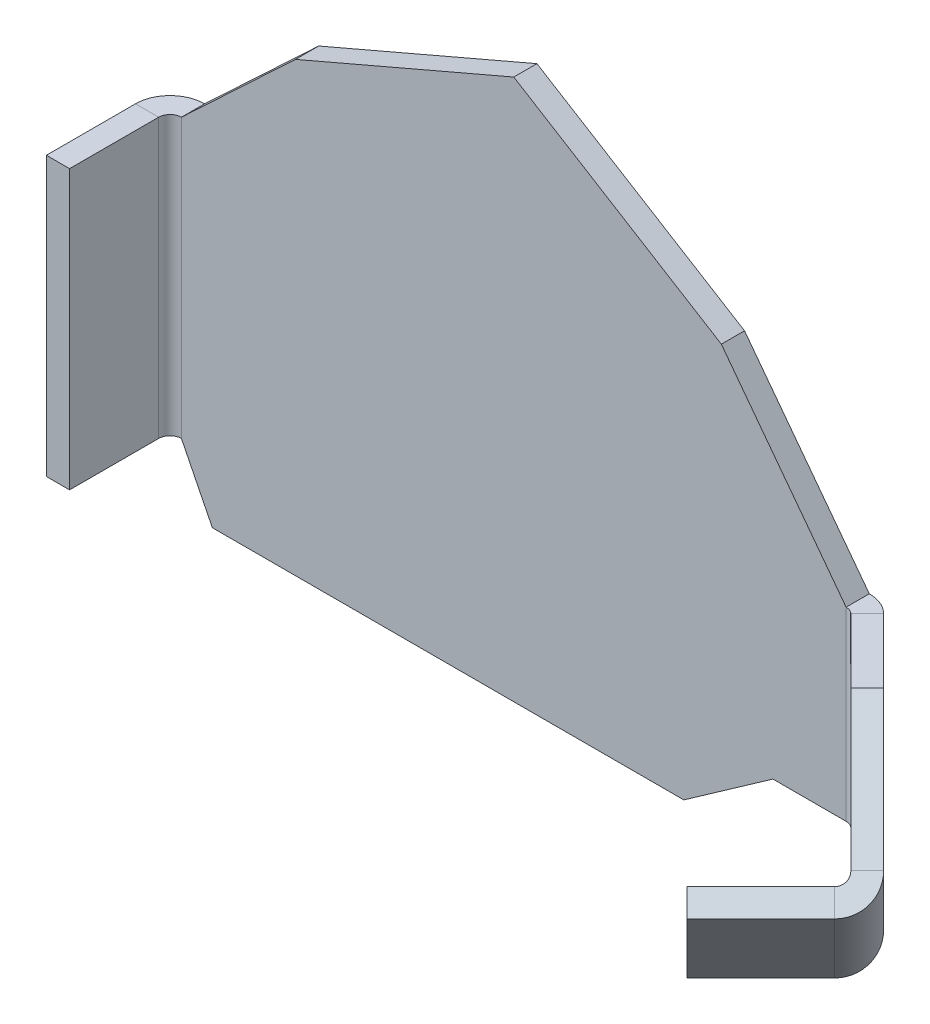
SolidWorks part; units mm, degrees
note: The reader was unsure of these and kept them because the rebuilt part matched: flange length of "Brida de arista1", "Brida de arista2", "Brida de arista3".
ref_plane "Alzado" through (0, 0, 0) normal (0, 0, 1) x (1, 0, 0)
ref_plane "Planta" through (0, 0, 0) normal (0, 1, 0) x (1, 0, 0)
ref_plane "Vista lateral" through (0, 0, 0) normal (1, 0, 0) x (0, 0, -1)
sketch "Croquis1" plane through (0, 0, 0) normal (0, 0, 1) x (1, 0, 0)
  line L1 (-21.5, -17.5) -> (21.5, -17.5)
  line L2 (-21.5, -17.5) -> (-21.5, 17.5)
  line L3 (-21.5, 17.5) -> (21.5, 17.5)
  line L4 (21.5, -17.5) -> (21.5, 17.5)
  line L5 (-21.5, -17.5) -> (21.5, 17.5) construction
  line L6 (-21.5, 17.5) -> (21.5, -17.5) construction
  point P0 (0, 0)
  dimension "D1" = 43
  dimension "D2" = 35
base flange "Brida base1" sketch "Croquis1" thickness 1.5 reverse thickness direction no parameters "D1"=0.7366
sketch "Croquis6" plane through (0, 0, 0) normal (0, 0, 1) x (1, 0, 0)
  line L0 (11, -17.5) -> (16.7649, -13.45)
  line L1 (-21.5, -13.5) -> (-21.5, 4.5)
  line L2 (-21.5, 4.5) -> (-14.1215, 11.428)
  line L3 (-21.5, -17.5) -> (21.5, -17.5) construction
  line L4 (16.7649, -13.45) -> (21.5, -13.45)
  line L5 (-14.1215, 11.428) -> (0, 17.5)
  line L6 (21.5, -17.5) -> (21.5, 17.5) construction
  line L7 (21.5, -13.45) -> (21.5, -1.45)
  line L8 (11, -17.5) -> (-19.5, -17.5)
  line L9 (-19.5, -17.5) -> (-21.5, -13.5)
  line L10 (-21.5, 17.5) -> (-21.5, -17.5) construction
  line L11 (21.5, 17.5) -> (-21.5, 17.5) construction
  line L13 (0, 17.5) -> (13.4297, 9.2474)
  line L14 (13.4297, 9.2474) -> (21.5, -1.45)
  line L16 (-29.7834, -22.9401) -> (29.7834, -22.9401)
  line L17 (-29.7834, -22.9401) -> (-29.7834, 22.9401)
  line L18 (-29.7834, 22.9401) -> (29.7834, 22.9401)
  line L19 (29.7834, -22.9401) -> (29.7834, 22.9401)
  line L21 (-29.7834, 22.9401) -> (0, 0) construction
  line L22 (0, 0) -> (29.7834, 22.9401) construction
  point P12 (0, 0)
  dimension "D1" = 12
  dimension "D2" = 4.05
  dimension "D3" = 10.5
  dimension "D4" = 30.5
  dimension "D5" = 4
  dimension "D6" = 18
extrude "Cortar-Extruir1" cut sketch "Croquis6" against normal blind 10 normal cut yes
edge flange "Brida de arista1" sketch "Croquis9" flange angle 90 flange length 8 flange position bend outside bend radius 0.7366 thickness 1.5 relief rectangular parameters "D6"=10
sketch "Croquis9" plane through (-21.5, 0, 0) normal (-1, 0, 0) x (0, -1, 0)
  line L2 (-4.5, 0) -> (-4.5, 6.5)
  line L3 (-4.5, 6.5) -> (13.5, 6.5)
  line L4 (13.5, 6.5) -> (13.5, 0)
  line L5 (-4.5, 0) -> (13.5, 0) construction
  line L6 (-4.5, 0) -> (13.5, 0)
bend "Pliegue de arista1" bend radius 0.7366 bend angle 90 parameters "D5"=1
edge flange "Brida de arista2" sketch "Croquis12" flange angle 135 flange length 21 flange position bend outside bend radius 0.7366 thickness 1.5 relief rectangular parameters "D6"=10
sketch "Croquis12" plane through (21.5, 0, 0) normal (0.7071, 0, -0.7071) x (0, 1, 0)
  line L2 (-13.45, 0) -> (-13.45, 20.3787)
  line L3 (-13.45, 20.3787) -> (-1.45, 20.3787)
  line L4 (-1.45, 20.3787) -> (-1.45, 0)
  line L5 (-13.45, 0) -> (-1.45, 0) construction
  line L6 (-13.45, 0) -> (-1.45, 0)
bend "Pliegue de arista2" bend radius 0.7366 bend angle 45 parameters "D5"=2
sketch "Croquis13" plane through (11.9632, 0, -11.9632) normal (0.7071, 0, -0.7071) x (-0.7071, 0, -0.7071)
  line L0 (-35.7972, -1.45) -> (-23.7972, -13.45)
  line L1 (-35.7972, -13.45) -> (-15.7237, -13.45) construction
  line L2 (-15.7237, -1.45) -> (-35.7972, -1.45) construction
  line L3 (-35.7972, -1.45) -> (-35.7972, -13.45)
  line L4 (-35.7972, -13.45) -> (-23.7972, -13.45)
  dimension "D1" = 45
extrude "Cortar-Extruir2" cut sketch "Croquis13" against normal blind 10 normal cut yes
sketch "Croquis14" plane through (11.9632, 0, -11.9632) normal (0.7071, 0, -0.7071) x (-0.7071, 0, -0.7071)
  line L0 (-35.7972, -1.45) -> (-23.7972, -1.45)
  line L1 (-15.7237, -1.45) -> (-35.7972, -1.45) construction
  line L2 (-23.7972, -1.45) -> (-30.1612, 4.914)
  line L3 (-30.1612, 4.914) -> (-36.1612, -1.086)
  line L4 (-35.7972, -1.45) -> (-36.1612, -1.086)
  dimension "D1" = 12
  dimension "D2" = 9
  dimension "D3" = 135
extrude "Saliente-Extruir1" add sketch "Croquis14" against normal up to surface (1.5 mm away) up to face at (26.9966, -7.45, 5.1915)
sketch "Croquis15" plane through (10.9026, 0, -10.9026) normal (-0.7071, 0, 0.7071) x (0.7071, 0, 0.7071)
  line L0 (30.1612, 4.914) -> (36.1612, -1.086)
  line L1 (36.1612, -1.086) -> (35.1005, -2.1467)
  line L2 (36.1612, -1.086) -> (23.7972, -13.45) construction
  line L3 (35.1005, -2.1467) -> (29.1005, 3.8533)
  line L4 (23.7972, -1.45) -> (30.1612, 4.914) construction
  line L5 (29.1005, 3.8533) -> (30.1612, 4.914)
  dimension "D1" = 1.5
extrude "Cortar-Extruir3" cut sketch "Croquis15" against normal blind 10 normal cut yes
edge flange "Brida de arista3" sketch "Croquis18" flange angle 90 flange length 9 flange position bend outside bend radius 0.7366 thickness 1.5 relief rectangular parameters "D6"=10
sketch "Croquis18" plane through (24.0714, -18.6236, 2.2663) normal (0.5, -0.7071, 0.5) x (0.5, 0.7071, 0.5)
  line L0 (23.3019, 0) -> (7.3166, 0) construction
  line L1 (23.3019, 0) -> (7.3166, 0)
  line L2 (7.3166, 0) -> (7.3166, 7.5)
  line L3 (7.3166, 7.5) -> (23.3019, 7.5)
  line L4 (23.3019, 7.5) -> (23.3019, 0)
bend "Pliegue de arista3" bend radius 0.7366 bend angle 90 parameters "D5"=3
sketch "Líneas de pliegue1" [suppressed] plane through (0, 0, 0) normal (0, 1, 0) x (1, 0, 0)
sketch "Cuadro delimitador1" [suppressed] plane through (0, 0, 0) normal (0, 1, 0) x (1, 0, 0)
sheet metal parameters "Chapa metálica1" thickness 1.5 parameters "D1"=0.7366
flat pattern "Chapa desplegada1" [suppressed]
sketch "Líneas de pliegue2" plane through (0, 0, 0) normal (0, 1, 0) x (1, 0, 0)
sketch3d "Cuadro delimitador2" [suppressed]
  line L0 (24, -17.5, 0) -> (-24, -17.5, 0) construction
  line L1 (24, 17.5, 0) -> (-24, 17.5, 0) construction
  line L2 (24, -17.5, 0) -> (24, 17.5, 0) construction
  line L3 (-24, -17.5, 0) -> (-24, 17.5, 0) construction
sheet metal parameters "Chapa metálica2" thickness 1.5 parameters "D1"=0.7366
flat pattern "Chapa desplegada1"
sketch "Líneas de pliegue2" plane through (0, 0, 0) normal (0, 1, 0) x (1, 0, 0)
sketch3d "Cuadro delimitador2" [suppressed]
  line L0 (-21.5, -17.5, 0) -> (21.5, -17.5, 0) construction
  line L1 (-21.5, 17.5, 0) -> (21.5, 17.5, 0) construction
  line L2 (-21.5, -17.5, 0) -> (-21.5, 17.5, 0) construction
  line L3 (21.5, -17.5, 0) -> (21.5, 17.5, 0) construction
sheet metal parameters "Chapa metálica9" thickness 1.5 parameters "D1"=0.7366
flat pattern "Chapa desplegada1"
sketch "Líneas de pliegue2" plane through (0, 0, 0) normal (0, 0, 1) x (1, 0, 0)
  line L0 (-22.6676, 4.5) -> (-22.6676, -13.5) construction
  line L1 (-22.6676, 4.5) -> (-22.6676, -13.5) construction
sketch3d "Cuadro delimitador2" [suppressed]
  line L0 (-29.5985, -17.5, 0) -> (21.5, -17.5, 0) construction
  line L1 (-29.5985, 17.5, 0) -> (21.5, 17.5, 0) construction
  line L2 (-29.5985, -17.5, 0) -> (-29.5985, 17.5, 0) construction
  line L3 (21.5, -17.5, 0) -> (21.5, 17.5, 0) construction
bend of the flat pattern "Aplanar-<Pliegue de arista1>1"
sheet metal parameters "Chapa metálica10" thickness 1.5 parameters "D1"=0.7366
flat pattern "Chapa desplegada1"
sketch "Líneas de pliegue2" plane through (0, 0, 0) normal (0, 0, 1) x (1, 0, 0)
  line L0 (-22.6676, 4.5) -> (-22.6676, -13.5) construction
  line L1 (-22.6676, 4.5) -> (-22.6676, -13.5) construction
  line L2 (22.0838, -13.45) -> (22.0838, -1.45) construction
  line L3 (22.0838, -13.45) -> (22.0838, -1.45) construction
sketch3d "Cuadro delimitador2" [suppressed]
  line L0 (-29.5985, -17.5, 0) -> (42.7411, -17.5, 0) construction
  line L1 (-29.5985, 17.5, 0) -> (42.7411, 17.5, 0) construction
  line L2 (-29.5985, -17.5, 0) -> (-29.5985, 17.5, 0) construction
  line L3 (42.7411, -17.5, 0) -> (42.7411, 17.5, 0) construction
bend of the flat pattern "Aplanar-<Pliegue de arista1>1"
bend of the flat pattern "Aplanar-<Pliegue de arista2>1"
sheet metal parameters "Chapa metálica11" thickness 1.5 parameters "D1"=0.7366
flat pattern "Chapa desplegada1"
sketch "Líneas de pliegue2" plane through (0, 0, 0) normal (0, 0, 1) x (1, 0, 0)
  line L0 (-22.6676, 4.5) -> (-22.6676, -13.5) construction
  line L1 (-22.6676, 4.5) -> (-22.6676, -13.5) construction
  line L2 (22.0838, -13.45) -> (22.0838, -1.45) construction
  line L3 (22.0838, -13.45) -> (22.0838, -1.45) construction
sketch3d "Cuadro delimitador2" [suppressed]
  line L0 (-29.5985, -17.5, 0) -> (42.7411, -17.5, 0) construction
  line L1 (-29.5985, 17.5, 0) -> (42.7411, 17.5, 0) construction
  line L2 (-29.5985, -17.5, 0) -> (-29.5985, 17.5, 0) construction
  line L3 (42.7411, -17.5, 0) -> (42.7411, 17.5, 0) construction
bend of the flat pattern "Aplanar-<Pliegue de arista1>1"
bend of the flat pattern "Aplanar-<Pliegue de arista2>1"
sheet metal parameters "Chapa metálica12" thickness 1.5 parameters "D1"=0.7366
flat pattern "Chapa desplegada1"
sketch "Líneas de pliegue2" plane through (0, 0, 0) normal (0, 0, 1) x (1, 0, 0)
  line L0 (-22.6676, 4.5) -> (-22.6676, -13.5) construction
  line L1 (-22.6676, 4.5) -> (-22.6676, -13.5) construction
  line L2 (22.0838, -13.45) -> (22.0838, -1.45) construction
  line L3 (22.0838, -13.45) -> (22.0838, -1.45) construction
sketch3d "Cuadro delimitador2" [suppressed]
  line L0 (-29.5985, -17.5, 0) -> (43.1051, -17.5, 0) construction
  line L1 (-29.5985, 17.5, 0) -> (43.1051, 17.5, 0) construction
  line L2 (-29.5985, -17.5, 0) -> (-29.5985, 17.5, 0) construction
  line L3 (43.1051, -17.5, 0) -> (43.1051, 17.5, 0) construction
bend of the flat pattern "Aplanar-<Pliegue de arista1>1"
bend of the flat pattern "Aplanar-<Pliegue de arista2>1"
sheet metal parameters "Chapa metálica13" thickness 1.5 parameters "D1"=0.7366
flat pattern "Chapa desplegada1"
sketch "Líneas de pliegue2" plane through (0, 0, 0) normal (0, 0, 1) x (1, 0, 0)
  line L0 (-22.6676, 4.5) -> (-22.6676, -13.5) construction
  line L1 (-22.6676, 4.5) -> (-22.6676, -13.5) construction
  line L2 (22.0838, -13.45) -> (22.0838, -1.45) construction
  line L3 (22.0838, -13.45) -> (22.0838, -1.45) construction
sketch3d "Cuadro delimitador2" [suppressed]
  line L0 (-29.5985, -17.5, 0) -> (42.0444, -17.5, 0) construction
  line L1 (-29.5985, 17.5, 0) -> (42.0444, 17.5, 0) construction
  line L2 (-29.5985, -17.5, 0) -> (-29.5985, 17.5, 0) construction
  line L3 (42.0444, -17.5, 0) -> (42.0444, 17.5, 0) construction
bend of the flat pattern "Aplanar-<Pliegue de arista1>1"
bend of the flat pattern "Aplanar-<Pliegue de arista2>1"
sheet metal parameters "Chapa metálica14" thickness 1.5 parameters "D1"=0.7366
flat pattern "Chapa desplegada1"
sketch "Líneas de pliegue2" plane through (0, 0, 0) normal (0, 0, 1) x (1, 0, 0)
  line L0 (-22.6676, 4.5) -> (-22.6676, -13.5) construction
  line L1 (-22.6676, 4.5) -> (-22.6676, -13.5) construction
  line L2 (22.0838, -13.45) -> (22.0838, -1.45) construction
  line L3 (22.0838, -13.45) -> (22.0838, -1.45) construction
  line L4 (31.5667, -14.2756) -> (42.87, -2.9723) construction
  line L5 (31.5667, -14.2756) -> (42.87, -2.9723) construction
sketch3d "Cuadro delimitador2" [suppressed]
  line L0 (-29.0005, 18.7197, 0) -> (49.4874, 15.4186, 0) construction
  line L1 (-30.5044, -17.0372, 0) -> (47.9836, -20.3382, 0) construction
  line L2 (-29.0005, 18.7197, 0) -> (-30.5044, -17.0372, 0) construction
  line L3 (49.4874, 15.4186, 0) -> (47.9836, -20.3382, 0) construction
bend of the flat pattern "Aplanar-<Pliegue de arista1>1"
bend of the flat pattern "Aplanar-<Pliegue de arista2>1"
bend of the flat pattern "Aplanar-<Pliegue de arista3>1"
